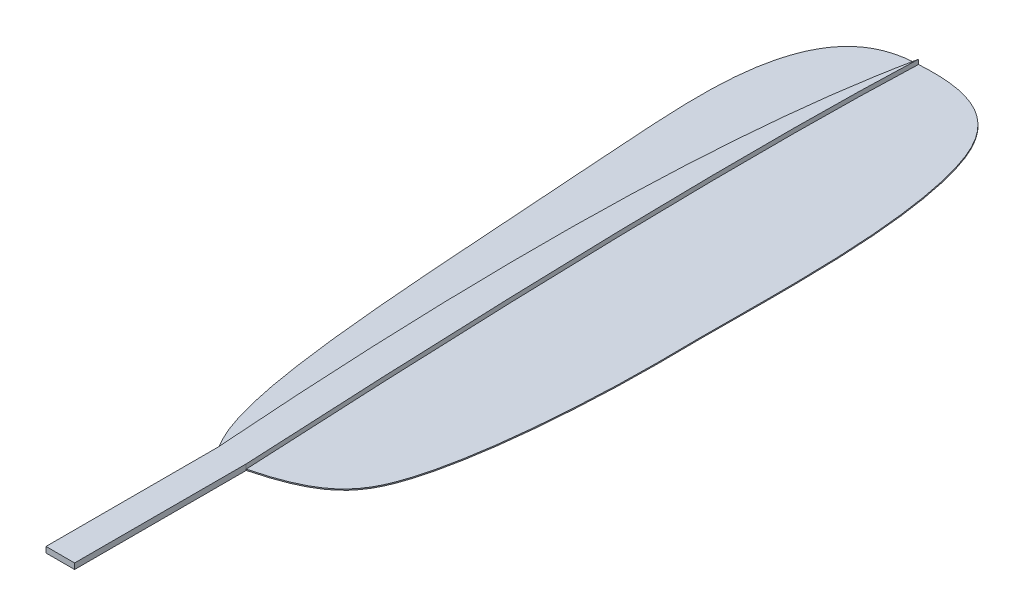
SolidWorks part; units mm, degrees
ref_plane "Front Plane" through (0, 0, 0) normal (0, 0, 1) x (1, 0, 0)
ref_plane "Top Plane" through (0, 0, 0) normal (0, 1, 0) x (1, 0, 0)
ref_plane "Right Plane" through (0, 0, 0) normal (1, 0, 0) x (0, 0, -1)
sketch "Sketch2" plane through (0, 0, 0) normal (0, 1, 0) x (1, 0, 0)
  line L0 (0, 0) -> (0, 120) construction
  line L1 (0, 0) -> (0, -30) construction
  line L3 (-2.5, 0) -> (2.5, 0) construction
  line L4 (-2.5, 0) -> (-2.5, -30)
  line L5 (-2.5, -30) -> (2.5, -30)
  line L6 (2.5, 0) -> (2.5, -30)
  spline S0 degree 3 poles (2.5, 0) (12.9322, 2.6928) (20.628, 11.5396) (22.5371, 45.0797) (22.0312, 66.371) (23.1434, 92.94) (16.0823, 117.6296) (8.9424, 120.5671) (0, 120) knots 0 0 0 0 0.1561 0.394681 0.460941 0.752435 0.809985 1 1 1 1
  spline S1 degree 2 poles (2.5, 0) (-1.6392, 79.8302) (0, 120) knots 0 0 0 1 1 1
  spline S2 degree 2 poles (-2.5, 0) (-8.3315, 79.8852) (0, 120) knots 0 0 0 1 1 1
  spline S3 degree 3 poles (0, 120) (-7.3575, 119.7562) (-16.1291, 114.5395) (-10.9604, 43.6234) (-9.5577, 8.3833) (-2.5, 0) knots 0 0 0 0 0.313532 0.413532 1 1 1 1
  point P10 (10.0606, 113.4257)
  point P12 (18.1675, 54.0195)
  point P14 (14.1805, 111.4322)
  point P15 (21.8887, 54.2853)
  point P16 (18.6991, 104.6543)
  point P17 (-9.2099, 84.3207)
  point P18 (17.0242, 102.9111)
  point P19 (13.9343, 105.0043)
  point P20 (15.8281, 105.0043)
  point P21 (17.2236, 95.9339)
  point P22 (17.9213, 91.6478)
  point P23 (22.307, 54.3694)
  point P24 (18.1478, 109.8169)
  point P25 (-15.7697, 96.1098)
  point P26 (-18.0709, 92.7081)
  point P27 (18.7481, 110.2171)
  point P28 (19.0483, 91.5075)
  point P29 (-14.6692, 73.5982)
  point P30 (19.3484, 88.706)
  point P31 (-14.7692, 72.8978)
  point P32 (18.5862, 108.5378)
  point P33 (-14.3106, 91.6071)
  dimension "D1" = 5
  dimension "40" = 30
  dimension "160" = 120
extrude "Boss-Extrude1" add sketch "Sketch2" along normal blind 1 contours S2 L4 L5 L6 S1 region at (-1.3307, 0, -34.7224)
extrude "Boss-Extrude2" add sketch "Sketch2<4>" along normal blind 0.2 contours S1 S0 | S2 S3 region at (-7.8803, 0, -71.2348) region at (10.4838, 0, -62.279)
sketch "Sketch2<4>" plane through (0, 0, 0) normal (0, 1, 0) x (1, 0, 0) same geometry as "Sketch2"
